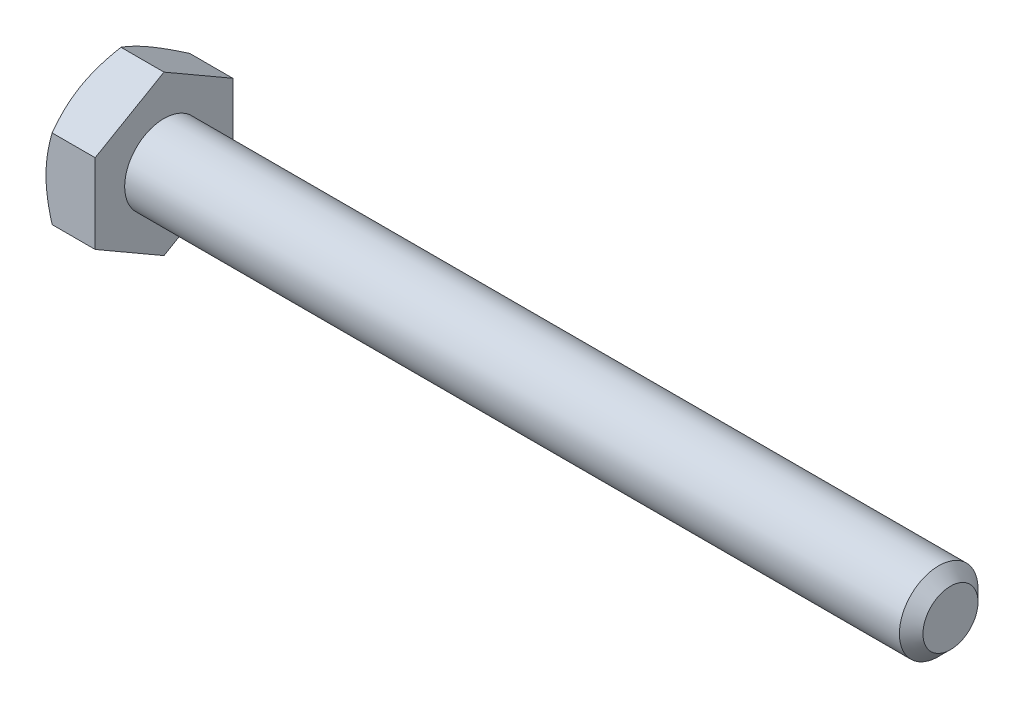
SolidWorks part; units mm, degrees
material "Alloy Steel"
ref_plane "Front Plane" through (0, 0, 0) normal (0, 0, 1) x (1, 0, 0)
ref_plane "Top Plane" through (0, 0, 0) normal (0, 1, 0) x (1, 0, 0)
ref_plane "Right Plane" through (0, 0, 0) normal (1, 0, 0) x (0, 0, -1)
sketch "Sketch1" plane through (0, 0, 0) normal (0, 0, 1) x (1, 0, 0)
  line L0 (-33.7344, 0) -> (33.7344, 0) construction
  line L1 (33.7344, 3.175) -> (33.7344, -3.175) construction
  line L2 (-29.7656, 5.5562) -> (-29.7656, -5.5562) construction
  line L3 (-33.7344, 5.5562) -> (-33.7344, -5.5562) construction
  point P9 (-29.7656, 0)
  point P10 (29.2894, -3.175)
  dimension "D1" = 4.445
  dimension "Screw Dia" = 6.35
  dimension "Hex" = 11.1125
  dimension "Head Ht" = 3.9688
  dimension "Screw Lenght" = 63.5
ref_plane "Plane2" through (33.7344, 0, 0) normal (1, 0, 0) x (0, 0, -1)
sketch "Sketch5" plane through (33.7344, 0, 0) normal (1, 0, 0) x (0, 0, -1)
  circle A0 centre (0, 0) radius 3.175
extrude "Boss-Extrude3" add sketch "Sketch5" against normal up to vertex (63.5 mm away) up to point (-29.7656, 0, 0)
sketch "Sketch9" plane through (33.7344, 0, 0) normal (1, 0, 0) x (0, 0, -1)
  circle A1 centre (0, 0) radius 3.175
  circle A2 centre (0, 0) radius 3.175
  dimension "D1" = 0
curve "Helix/Spiral1" [suppressed] pitch 1.27 height 20.32 turns 16 parameters "Pitch"=1.27
chamfer "Chamfer1" distance 0.9525 angle 45 1 edges at (33.7344, 0, -3.175)
sketch "Sketch10" plane through (0, 0, 0) normal (0, 0, 1) x (1, 0, 0)
  line L0 (33.7344, 3.175) -> (34.2106, 2.3501)
  line L1 (34.2106, 2.3501) -> (34.3694, 2.3501)
  line L2 (34.3694, 2.3501) -> (34.8456, 3.175)
  line L3 (33.7344, 3.175) -> (34.8456, 3.175)
  line L4 (34.29, 3.175) -> (34.29, 2.3501) construction
  line L5 (33.9725, 2.7626) -> (34.6075, 2.7626) construction
  dimension "D1" = 60
  dimension "D2" = 0.1588
  dimension "D3" = 0.635
sweep "Cut-Sweep1" [suppressed] cut profiles "Sketch10" path "Helix/Spiral1"
sketch "Sketch11" plane through (0, 0, 0) normal (0, 0, 1) x (1, 0, 0)
  line L0 (-29.7656, 3.175) -> (-29.7656, 0)
  line L1 (-29.7656, 0) -> (17.8594, 0)
  line L3 (17.8594, 0) -> (14.6844, 3.175)
  line L4 (-29.7656, 3.175) -> (14.6844, 3.175)
  dimension "D1" = 45
  dimension "MIn Thread" = 19.05
revolve "Revolve1" add sketch "Sketch11" angle 360 about L1
sketch "Sketch6" plane through (-29.7656, 0, 0) normal (-1, 0, 0) x (0, 0, 1)
  line L0 (0, 5.5562) -> (0, -5.5562) construction
  line L1 (5.5563, 3.2079) -> (0, 6.4158)
  line L2 (0, 6.4158) -> (-5.5562, 3.2079)
  line L3 (-5.5562, 3.2079) -> (-5.5562, -3.2079)
  line L4 (-5.5562, -3.2079) -> (0, -6.4158)
  line L5 (0, -6.4158) -> (5.5563, -3.2079)
  line L6 (5.5563, -3.2079) -> (5.5563, 3.2079)
  circle A0 centre (0, 0) radius 5.5563 construction
extrude "Boss-Extrude4" add sketch "Sketch6" along normal up to vertex (3.9688 mm away) up to point (-33.7344, -5.5562, 0)
sketch "Sketch7" plane through (-33.7344, 0, 0) normal (-1, 0, 0) x (0, 0, 1)
  circle A0 centre (0, 0) radius 5.5563 construction
  circle A1 centre (0, 0) radius 5.5563
sketch "Sketch8" plane through (-33.7344, 0, 0) normal (-1, 0, 0) x (0, 0, 1)
  circle A0 centre (0, 0) radius 5.5563 construction
  circle A1 centre (0, 0) radius 5.5563
extrude "Cut-Extrude3" cut sketch "Sketch8" against normal through all draft 60 flip side to cut
sketch "Sketch12" plane through (-33.7344, 0, 0) normal (-1, 0, 0) x (0, 0, 1)
  line L0 (0, 4.2783) -> (0, 2.3892) construction
  line L1 (0.1667, 4.2783) -> (0.1667, 2.3892)
  line L2 (-0.1667, 4.2783) -> (-0.1667, 2.3892)
  line L3 (0, 3.175) -> (0, -3.175) construction
  arc A0 (0.1667, 4.2783) -> (-0.1667, 4.2783) centre (0, 4.2783) ccw
  arc A1 (-0.1667, 2.3892) -> (0.1667, 2.3892) centre (0, 2.3892) ccw
  circle A3 centre (0, 0) radius 2.2225 construction
  circle A4 centre (0, 0) radius 4.445 construction
  point P2 (0, 3.3337)
  dimension "D1" = 4.445
  dimension "D3" = 8.89
  dimension "D2" = 0.3334
extrude "Cut-Extrude4" cut sketch "Sketch12" against normal blind 0.254
pattern_circular "CirPattern1" count 3 over 360 about axis through (-29.7656, 0, 0) along (1, 0, 0) of "Cut-Extrude4"
equation "\"D2@Sketch10\" = \"Pitch@Helix/Spiral1\"*.125"
equation "\"D3@Sketch10\" = \"Pitch@Helix/Spiral1\"*.5"
equation "\"D3@Helix/Spiral1\" = \"MIn Thread@Sketch11\"+\"Pitch@Helix/Spiral1\""
equation "\"D1@Chamfer1\" = \"Pitch@Helix/Spiral1\"*.75"
equation "\"D1@Sketch12\" = \"Hex@Sketch1\"*.4"
equation "\"D3@Sketch12\" = \"Hex@Sketch1\"*.8"
equation "\"D2@Sketch12\" = \"Hex@Sketch1\"*.03"
equation "\"D1@Sketch1\" = \"Pitch@Helix/Spiral1\"*3.5"
